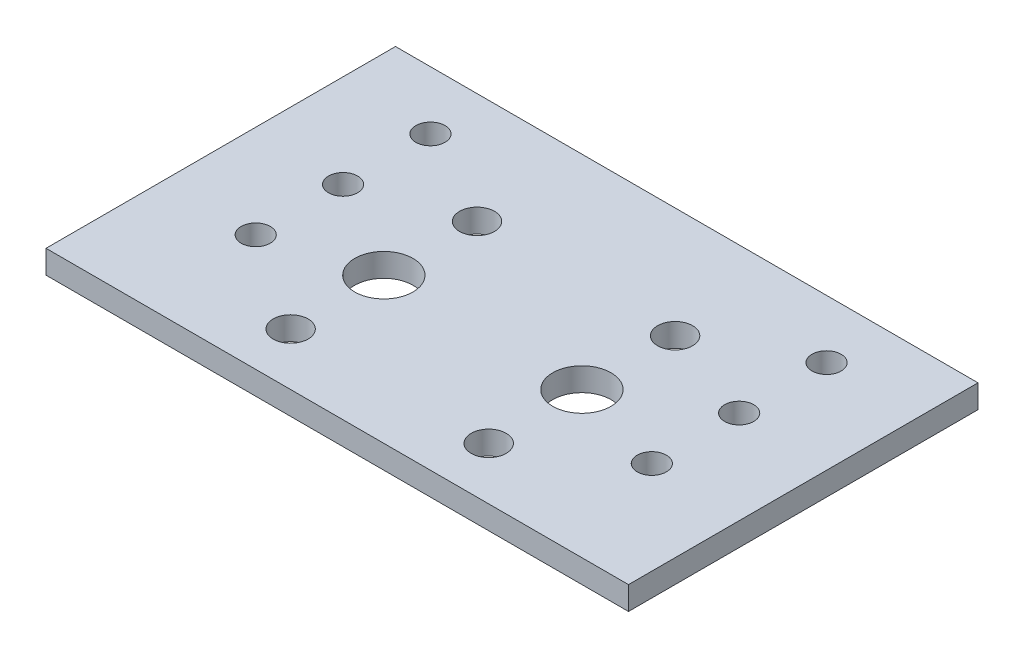
SolidWorks part; units mm, degrees
ref_plane "Спереди" through (0, 0, 0) normal (0, 0, 1) x (1, 0, 0)
ref_plane "Сверху" through (0, 0, 0) normal (0, 1, 0) x (1, 0, 0)
ref_plane "Справа" through (0, 0, 0) normal (1, 0, 0) x (0, 0, -1)
sketch "Эскиз1" plane through (0, 0, 0) normal (0, 1, 0) x (1, 0, 0)
  line L0 (16, 60) -> (16, 0) construction
  line L1 (0, 0) -> (100, 0)
  line L2 (0, 0) -> (0, 60)
  line L3 (0, 60) -> (100, 60)
  line L4 (100, 0) -> (100, 60)
  line L5 (84, 60) -> (84, 0) construction
  line L6 (33, 25) -> (67, 25) construction
  line L7 (50, 60) -> (50, 0) construction
  line L8 (33, 38.1007) -> (33, 6.4976) construction
  line L9 (67, 43.8556) -> (67, 6.4976) construction
  circle A0 centre (16, 50) radius 2.5
  circle A1 centre (16, 35) radius 2.5
  circle A2 centre (16, 20) radius 2.5
  circle A3 centre (84, 50) radius 2.5
  circle A4 centre (84, 35) radius 2.5
  circle A5 centre (84, 20) radius 2.5
  circle A6 centre (33, 25) radius 5
  circle A7 centre (67, 25) radius 5
  circle A8 centre (33, 41) radius 3
  circle A9 centre (33, 9) radius 3
  circle A10 centre (67, 41) radius 3
  circle A11 centre (67, 9) radius 3
  dimension "D5" = 5
  dimension "D6" = 5
  dimension "D7" = 5
  dimension "D12" = 10
  dimension "D13" = 10
  dimension "D17" = 6
  dimension "D18" = 6
  dimension "D19" = 6
  dimension "D20" = 6
  dimension "D1" = 100
  dimension "D2" = 60
  dimension "D3" = 16
  dimension "D4" = 16
  dimension "D8" = 10
  dimension "D9" = 15
  dimension "D10" = 15
  dimension "D14" = 17
  dimension "D15" = 17
  dimension "D16" = 35
  dimension "D21" = 16
  dimension "D22" = 16
  dimension "D23" = 16
  dimension "D24" = 16
  dimension "D11" = 2
extrude "Бобышка-Вытянуть1" add sketch "Эскиз1" along normal blind 4
